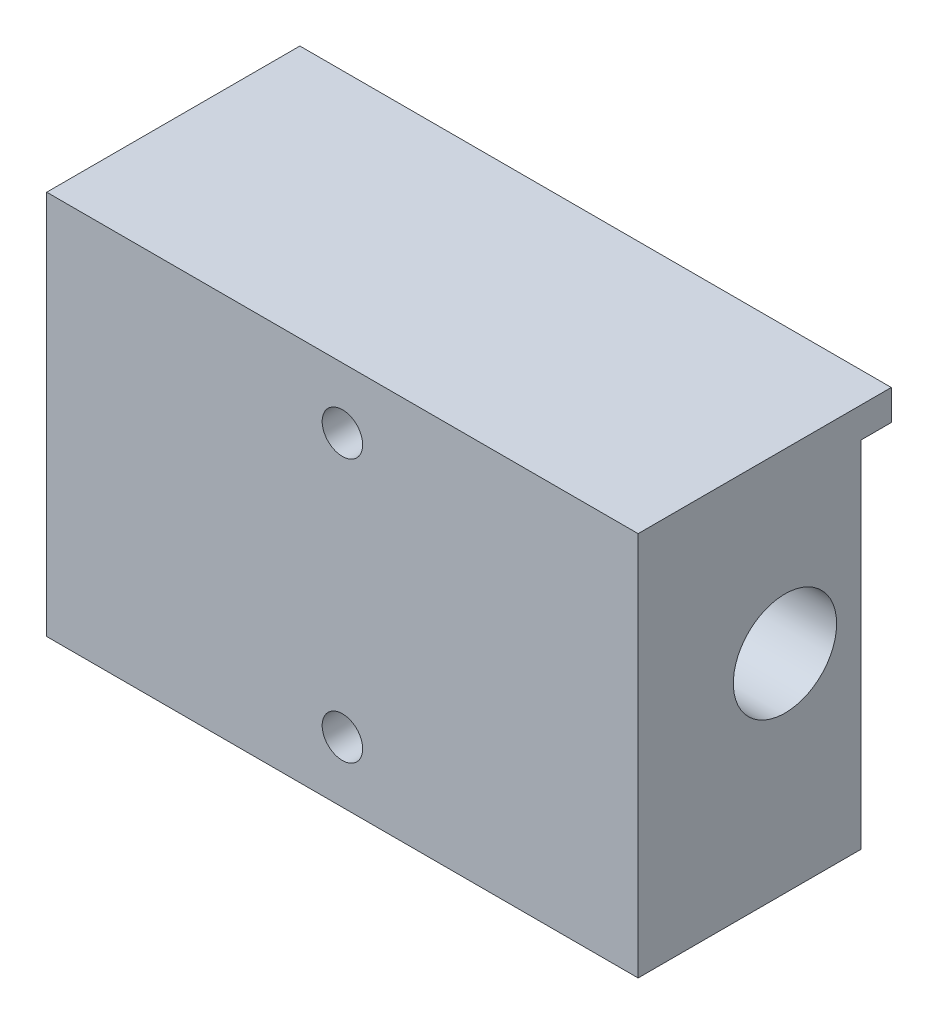
SolidWorks part; units mm, degrees
ref_plane "Alzado" through (0, 0, 0) normal (0, 0, 1) x (1, 0, 0)
ref_plane "Planta" through (0, 0, 0) normal (0, 1, 0) x (1, 0, 0)
ref_plane "Vista lateral" through (0, 0, 0) normal (1, 0, 0) x (0, 0, -1)
sketch "Croquis1" plane through (0, 0, 0) normal (0, 0, 1) x (1, 0, 0)
  line L1 (0, 0) -> (58.4, 0)
  line L2 (0, 0) -> (0, 38)
  line L3 (0, 38) -> (58.4, 38)
  line L4 (58.4, 0) -> (58.4, 38)
  dimension "D1" = 38
  dimension "D2" = 58.4
extrude "Saliente-Extruir1" add sketch "Croquis1" along normal blind 22
sketch "Croquis2" plane through (58.4, 0, 0) normal (1, 0, 0) x (0, 0, -1)
  line L0 (-22, 0) -> (-22, 38) construction
  line L1 (-22, 38) -> (0, 38) construction
  circle A0 centre (-7.5, 20.5) radius 5.1
  dimension "D1" = 10.2
  dimension "D2" = 14.5
  dimension "D3" = 17.5
extrude "Cortar-Extruir1" cut sketch "Croquis2" against normal through all
hole_wizard "Taladros de espiga de Ø4.0mm2" positions "Croquis4" profile "Croquis5" hole size "Ø4.0" standard "DIN"
sketch "Croquis4" plane through (0, 0, 22) normal (0, 0, 1) x (1, 0, 0)
  line L0 (0, 32) -> (58.4, 32) construction
  line L1 (0, 38) -> (0, 0) construction
  line L2 (58.4, 0) -> (58.4, 38) construction
  line L5 (58.4, 6) -> (0, 6) construction
  line L7 (58.4, 38) -> (0, 38) construction
  line L8 (29.2, 38) -> (29.2, 0) construction
  line L9 (0, 0) -> (58.4, 0) construction
  point P24 (29.2, 32)
  point P26 (29.2, 6)
  dimension "D1" = 6
  dimension "D2" = 6
sketch "Croquis5" plane through (29.2, 6, 22) normal (1, 0, 0) x (0, -1, 0)
  line L0 (0, 0) -> (0, 15.2017)
  line L1 (0, 15.2017) -> (2, 14)
  line L2 (2, 14) -> (2, 0)
  line L5 (2, 0) -> (0, 0)
  line L10 (0, 15.2017) -> (-2, 14) construction
  line L11 (0, -6.35) -> (0, 107.95) construction
  dimension "Diámetro de taladro" = 4
  dimension "Profundidad de taladro" = 14
  dimension "Ángulo de perforador" = 118
sketch "Croquis6" plane through (0, 0, 0) normal (0, 0, -1) x (-1, 0, 0)
  line L1 (-58.4, 35) -> (0, 35)
  line L2 (-58.4, 35) -> (-58.4, 38)
  line L3 (-58.4, 38) -> (0, 38)
  line L4 (0, 35) -> (0, 38)
  dimension "D1" = 3
extrude "Saliente-Extruir2" add sketch "Croquis6" along normal blind 3
hole_wizard "Perforador para roscar para macho de roscar para M33" positions "Croquis10" profile "Croquis11" hole size "M3" standard "DIN"
sketch "Croquis10" plane through (0, 0, 0) normal (-1, 0, 0) x (0, 0, 1)
  line L0 (7.5, 12.5) -> (7.5, 28.5) construction
  line L2 (15.5, 20.5) -> (7.5, 20.5) construction
  circle A0 centre (7.5, 20.5) radius 8 construction
  point P5 (7.5, 12.5)
  point P6 (7.5, 28.5)
  point P8 (15.5, 20.5)
  dimension "D1" = 16
sketch "Croquis11" plane through (0, 20.5, 15.5) normal (0, 1, 0) x (0, 0, 1)
  line L0 (0, 0) -> (0, 14.7511)
  line L1 (0, 14.7511) -> (1.25, 14)
  line L2 (1.25, 14) -> (1.25, 0)
  line L5 (1.25, 0) -> (0, 0)
  line L10 (0, 14.7511) -> (-1.25, 14) construction
  line L11 (0, -6.35) -> (0, 107.95) construction
  dimension "Diámetro de taladro" = 2.5
  dimension "Profundidad de taladro" = 14
  dimension "Ángulo de perforador" = 118
